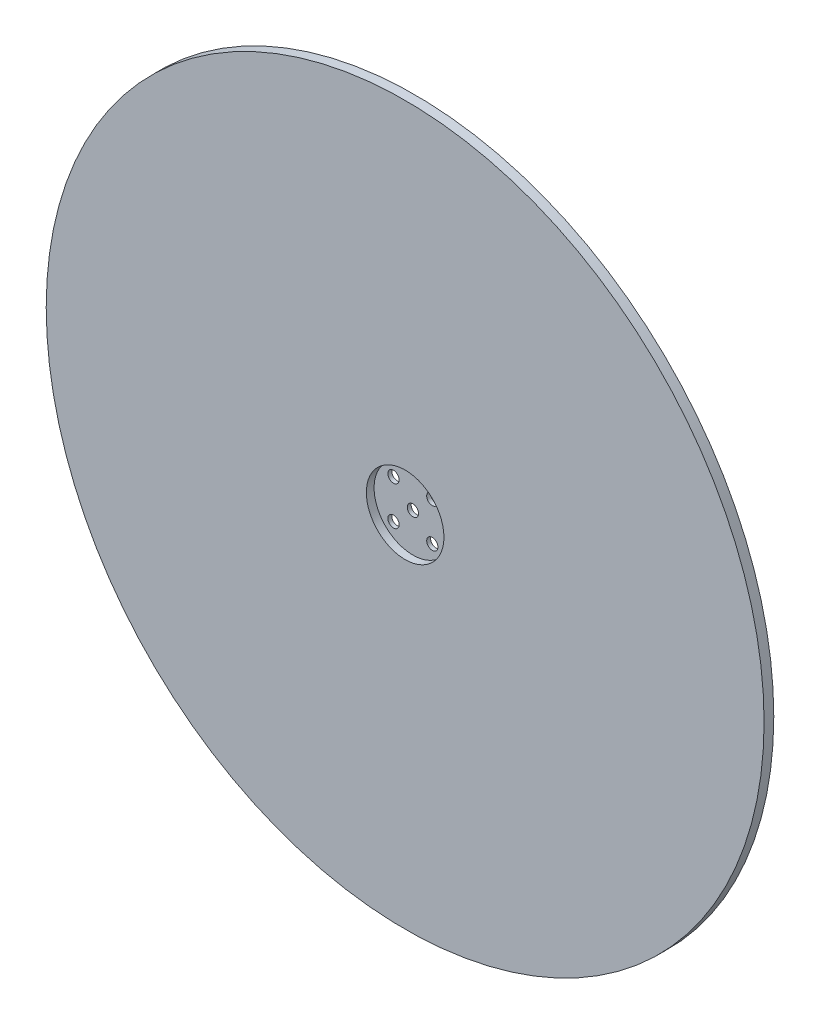
SolidWorks part; units mm, degrees
material "PEI"
ref_plane "Ground" through (0, 0, 0) normal (0, 0, 1) x (1, 0, 0)
ref_plane "Right" through (0, 0, 0) normal (0, 1, 0) x (1, 0, 0)
ref_plane "Front" through (0, 0, 0) normal (1, 0, 0) x (0, 0, -1)
sketch "Sketch1" plane through (0, 0, 0) normal (0, 0, 1) x (1, 0, 0)
  line L1 (-5, -5) -> (5, -5) construction
  line L2 (-5, -5) -> (-5, 5) construction
  line L3 (-5, 5) -> (5, 5) construction
  line L4 (5, -5) -> (5, 5) construction
  line L5 (-5, -5) -> (5, 5) construction
  line L6 (-5, 5) -> (5, -5) construction
  circle A0 centre (0, 0) radius 10
  circle A1 centre (0, 0) radius 92.5
  circle A2 centre (0, 0) radius 1.45
  circle A3 centre (-5, 5) radius 1.45
  circle A4 centre (5, 5) radius 1.45
  circle A5 centre (5, -5) radius 1.45
  circle A6 centre (-5, -5) radius 1.45
  dimension "D1" = 20
  dimension "D2" = 185
  dimension "D4" = 2.9
  dimension "D3" = 10
extrude "Boss-Extrude1" add sketch "Sketch1" against normal blind 1 contours A0 A6 A5 A4 A3 A2 region at (-9.7172, 0, 0)
ref_plane "Plane1" through (-2.5, 0, 0) normal (-1, 0, 0) x (0, 0, 1)
extrude "Boss-Extrude2" add sketch "Sketch1<4>" along normal blind 2 and the other way blind 0.5 contours A1 A0 region at (-89.8837, 0, 0)
sketch "Sketch1<4>" plane through (0, 0, 0) normal (0, 0, 1) x (1, 0, 0) same geometry as "Sketch1"
sketch "Sketch2" plane through (-2.5, 0, 0) normal (1, 0, 0) x (0, 0, -1)
  line L0 (10.5, -61.233) -> (10.5, 64.767) construction
  line L1 (-2, -92.5) -> (0.5, -92.5)
  line L2 (-2, -92.5) -> (-2, 92.5)
  line L3 (-2, 92.5) -> (0.5, 92.5)
  line L5 (10.5, -65.233) -> (0.5, -65.233)
  line L6 (10.5, -57.233) -> (0.5, -57.233)
  line L7 (0.5, -65.233) -> (0.5, -57.233)
  line L8 (0.5, 60.767) -> (0.5, 68.767)
  line L9 (10.5, 68.767) -> (0.5, 68.767)
  line L10 (10.5, 60.767) -> (0.5, 60.767)
  line L11 (10.5, 68.767) -> (0.5, 70.267)
  line L12 (0.5, 68.767) -> (0.5, 70.267)
  line L14 (0.5, -92.5) -> (-2, -92.5)
  line L15 (0.5, -92.5) -> (0.5, 92.5)
  line L16 (0.5, 92.5) -> (-2, 92.5)
  line L17 (-2, -92.5) -> (-2, 92.5)
  circle A0 centre (10.5, -61.233) radius 1.5
  circle A1 centre (10.5, 64.767) radius 1.5
  arc A2 (10.5, -65.233) -> (10.5, -57.233) centre (10.5, -61.233) ccw
  arc A3 (10.5, 60.767) -> (10.5, 68.767) centre (10.5, 64.767) ccw
  dimension "D1" = 3
  dimension "D3" = 4
  dimension "D2" = 126
  dimension "D4" = 10
  dimension "D6" = 61.233
  dimension "D7" = 64.767
  dimension "D8" = 1.5
  dimension "D5" = 2
extrude "Boss-Extrude3" add sketch "Sketch2" against normal blind 8 contours A0 A2 L5 L15 L6 | A3 A1 L10 L15 L9 region at (-2.5, -61.233, -6.8561) region at (-2.5, 64.767, -6.8561)
fillet "Fillet4" radius 5 5 edges at (-10.5, 64.767, -0.5) (-6.5, 60.767, -0.5) (-10.5, -61.233, -0.5) (-6.5, -57.233, -0.5) (-6.5, -65.233, -0.5)
fillet "Fillet5" radius 1 4 edges at (10, 0, -0.5) (-2.5, 62.267, -0.5) (-2.5, -61.233, -0.5) (-9, 68.767, -0.5)
sketch "Sketch3" plane through (-10.5, 0, 0) normal (-1, 0, 0) x (0, 0, 1)
  circle A0 centre (-10.5, -61.233) radius 1.5 construction
  circle A1 centre (-10.5, -61.233) radius 1.5
  circle A2 centre (-10.5, -61.233) radius 2.75
  arc A3 (-10.5, -57.233) -> (-10.5, -65.233) centre (-10.5, -61.233) ccw construction
  arc A4 (-10.5, -57.233) -> (-10.5, -65.233) centre (-10.5, -61.233) ccw
  circle A5 centre (-10.5, 64.767) radius 2.75
  circle M7 centre (-10.5, -61.233) radius 1.5
  dimension "D1" = 5.5
  dimension "D2" = 2
extrude "Cut-Extrude1" cut sketch "Sketch3" against normal blind 3 contours A5 | A2 M7 region at (-10.5, -61.233, -13.1722) region at (-10.5, 64.767, -10.5)
